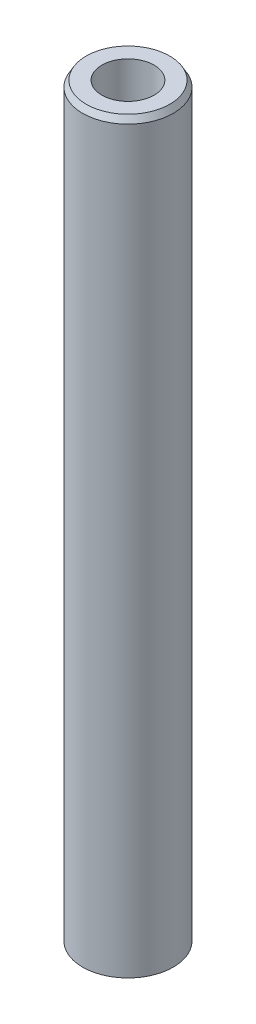
SolidWorks part; units mm, degrees
ref_plane "Front Plane" through (0, 0, 0) normal (0, 0, 1) x (1, 0, 0)
ref_plane "Top Plane" through (0, 0, 0) normal (0, 1, 0) x (1, 0, 0)
ref_plane "Right Plane" through (0, 0, 0) normal (1, 0, 0) x (0, 0, -1)
sketch "Sketch1" plane through (0, 0, 0) normal (0, 1, 0) x (1, 0, 0)
  circle A0 centre (0, 0) radius 32.5
  dimension "SHAFT_OD" = 65
extrude "Boss-Extrude1" add sketch "Sketch1" along normal blind 537.1533
sketch "Sketch2" plane through (0, 0, 0) normal (0, 1, 0) x (1, 0, 0)
  circle A0 centre (0, 0) radius 18.721
  dimension "BORE_D" = 37.442
extrude "Cut-Extrude1" cut sketch "Sketch2" along normal through all
chamfer "Chamfer1" distance 4.3804 angle 30 2 edges at (0, 537.1533, 32.5) (0, 0, 32.5) first distance on face at (0, 537.1533, 32.5) first distance on face at (0, 0, 18.721)
